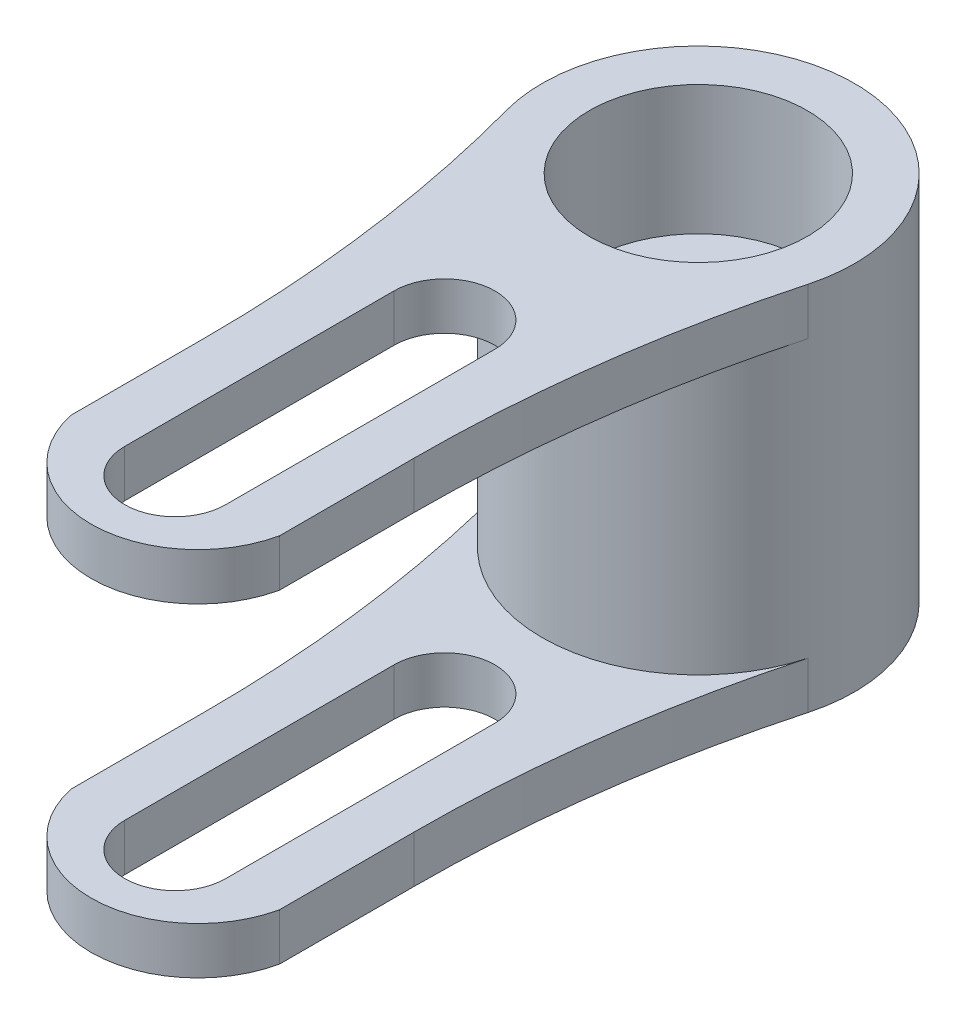
SolidWorks part; units mm, degrees
ref_plane "Front Plane" through (0, 0, 0) normal (0, 0, 1) x (1, 0, 0)
ref_plane "Top Plane" through (0, 0, 0) normal (0, 1, 0) x (1, 0, 0)
ref_plane "Right Plane" through (0, 0, 0) normal (1, 0, 0) x (0, 0, -1)
sketch "Sketch1" plane through (0, 0, 0) normal (0, 1, 0) x (1, 0, 0)
  line L0 (0, 5.8) -> (0, 4.05) construction
  line L1 (0, -9.425) -> (0, -19.425) construction
  line L2 (-3.875, -14.425) -> (-3.875, -19.425)
  line L3 (3.875, -19.425) -> (3.875, -14.425)
  line L4 (1.875, -9.425) -> (1.875, -19.425)
  line L5 (-1.875, -9.425) -> (-1.875, -19.425)
  line L6 (0, -7.55) -> (0, -5.8) construction
  line L7 (-3.875, -14.425) -> (3.875, -14.425) construction
  circle A0 centre (0, 0) radius 4.05
  circle A1 centre (0, 0) radius 5.8
  arc A2 (1.875, -9.425) -> (-1.875, -9.425) centre (0, -9.425) ccw
  arc A3 (-5.597, -1.5209) -> (-3.875, -14.425) centre (-53.0844, -14.425) cw
  arc A4 (-3.875, -19.425) -> (3.875, -19.425) centre (0, -19.425) ccw
  arc A5 (3.875, -14.425) -> (5.597, -1.5209) centre (53.0844, -14.425) cw
  arc A6 (-1.875, -19.425) -> (1.875, -19.425) centre (0, -19.425) ccw
  point P6 (0, -14.425)
  dimension "D1" = 8.1
  dimension "D2" = 1.75
  dimension "D3" = 3.75
  dimension "D4" = 2
  dimension "D5" = 10
  dimension "D6" = 1.75
extrude "Boss-Extrude1" add sketch "Sketch1" along normal mid plane 13.775 contours L3 A5 A1 A3 L2 A4 A6 L5 A2 L4 | A0 | A1 A0 region at (-4.0647, 0, 7.8834) region at (-0.7455, 0, -5.5864) region at (0, 0, 0)
ref_plane "Plane1" through (0, -5.1375, 0) normal (0, -1, 0) x (-1, 0, 0)
ref_plane "Plane2" through (0, 5.1375, 0) normal (0, 1, 0) x (1, 0, 0)
extrude "Cut-Extrude1" cut sketch "Sketch1<4>" along normal up to surface (10.275 mm away) from surface contours L3 A5 A1 A3 L2 A4 A6 L5 A2 L4 region at (-4.0647, 0, 7.8834) up to plane "Plane2" starting at plane "Plane1"
sketch "Sketch1<4>" plane through (0, 0, 0) normal (0, 1, 0) x (1, 0, 0) same geometry as "Sketch1"
extrude "Cut-Extrude2" cut sketch "Sketch1<5>" against normal blind 4.8 from surface contours A0 region at (0, 0, 0) starting at face at (0, 6.8875, 14.425)
sketch "Sketch1<5>" plane through (0, 0, 0) normal (0, 1, 0) x (1, 0, 0) same geometry as "Sketch1"
sketch "Sketch4" plane through (0, -6.8875, 0) normal (0, -1, 0) x (1, 0, 0)
  line L2 (0, 22.55) -> (0, 23.3) construction
  line L4 (0, 22.55) -> (0, 21.3) construction
  arc A0 (3.875, 19.425) -> (-3.875, 19.425) centre (0, 19.425) ccw construction
  arc A1 (1.875, 19.425) -> (-1.875, 19.425) centre (0, 19.425) ccw construction
  arc A3 (-3.875, 19.425) -> (3.875, 19.425) centre (0, 18.585) cw
  arc A4 (3.875, 19.425) -> (-3.875, 19.425) centre (0, 19.425) ccw
  dimension "D1" = 0.75
extrude "Cut-Extrude3" cut sketch "Sketch4" against normal through all
equation "\"D1@Boss-Extrude1\"=9.525mm+1.75mm+1.75mm+.75mm"
